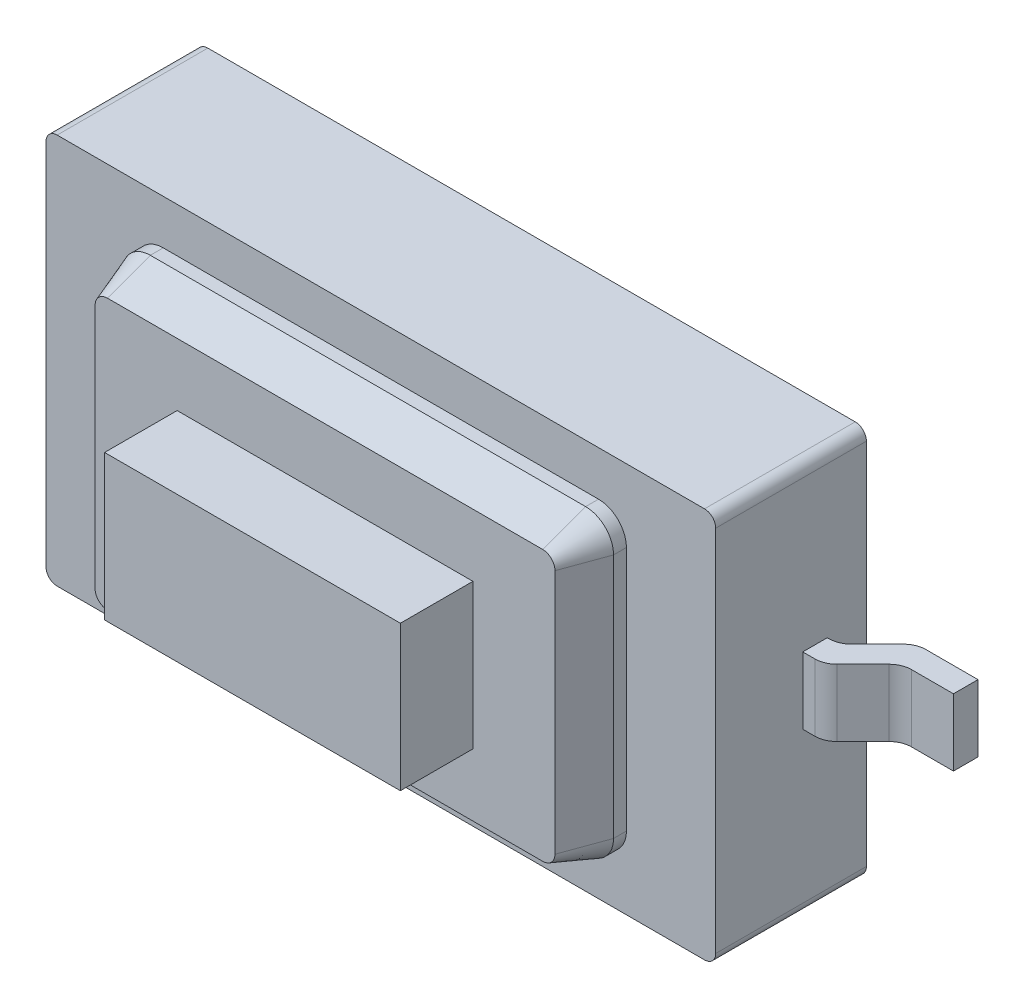
SolidWorks part; units mm, degrees
ref_plane "Front Plane" through (0, 0, 0) normal (0, 0, 1) x (1, 0, 0)
ref_plane "Top Plane" through (0, 0, 0) normal (0, 1, 0) x (1, 0, 0)
ref_plane "Right Plane" through (0, 0, 0) normal (1, 0, 0) x (0, 0, -1)
sketch "Sketch1" plane through (0, 0, 0) normal (0, 0, 1) x (1, 0, 0)
  line L0 (0, 6.8947) -> (0, -7.2797) construction
  line L2 (10.797, 0) -> (-8.2771, 0) construction
  line L3 (-2.9, 1.75) -> (2.9, 1.75)
  line L4 (-3, 1.65) -> (-3, -1.65)
  line L5 (-2.9, -1.75) -> (2.9, -1.75)
  line L6 (3, 1.65) -> (3, -1.65)
  line L7 (-1.325, 0.65) -> (1.325, 0.65)
  line L8 (-1.325, 0.65) -> (-1.325, -0.65)
  line L9 (-1.325, -0.65) -> (1.325, -0.65)
  line L10 (1.325, 0.65) -> (1.325, -0.65)
  line L11 (-1.95, 1.35) -> (1.95, 1.35)
  line L12 (-2.2, 1.1) -> (-2.2, -1.1)
  line L13 (-1.95, -1.35) -> (1.95, -1.35)
  line L14 (2.2, 1.1) -> (2.2, -1.1)
  arc A0 (-2.2, -1.1) -> (-1.95, -1.35) centre (-1.95, -1.1) ccw
  arc A1 (1.95, -1.35) -> (2.2, -1.1) centre (1.95, -1.1) ccw
  arc A2 (1.95, 1.35) -> (2.2, 1.1) centre (1.95, 1.1) cw
  arc A3 (-1.95, 1.35) -> (-2.2, 1.1) centre (-1.95, 1.1) ccw
  arc A4 (-3, -1.65) -> (-2.9, -1.75) centre (-2.9, -1.65) ccw
  arc A5 (2.9, -1.75) -> (3, -1.65) centre (2.9, -1.65) ccw
  arc A6 (2.9, 1.75) -> (3, 1.65) centre (2.9, 1.65) cw
  arc A7 (-2.9, 1.75) -> (-3, 1.65) centre (-2.9, 1.65) ccw
  dimension "D7" = 0.25
  dimension "D8" = 0.1
  dimension "D1" = 6
  dimension "D2" = 3.5
  dimension "D3" = 2.65
  dimension "D4" = 1.3
  dimension "D5" = 4.4
  dimension "D6" = 2.7
extrude "Boss-Extrude1" add sketch "Sketch1" along normal blind 1.35 contours L3 A6 L6 A5 L5 A4 L4 A7
extrude "Boss-Extrude2" add sketch "Sketch1<3>" along normal blind 1.85 contours L13 A1 L14 A2 L11 A3 L12 A0
sketch "Sketch1<3>" plane through (0, 0, 0) normal (0, 0, 1) x (1, 0, 0) same geometry as "Sketch1"
extrude "Boss-Extrude3" add sketch "Sketch1<4>" along normal blind 2.5 contours L9 L10 L7 L8
sketch "Sketch1<4>" plane through (0, 0, 0) normal (0, 0, 1) x (1, 0, 0) same geometry as "Sketch1"
chamfer "Chamfer1" distance 0.14 angle 70 7 edges at (0, -1.35, 1.85) (-2.1268, -1.2768, 1.85) (-2.2, 0, 1.85) (-2.1268, 1.2768, 1.85) (2.2, 0, 1.85) (2.1268, 1.2768, 1.85) (0, 1.35, 1.85) tangent propagation no first distance on face at (0, 0, 1.85)
sketch "Sketch2" plane through (0, 0, 0) normal (0, 1, 0) x (1, 0, 0)
  line L0 (3, -0.35) -> (3.0172, -0.35)
  line L1 (3.1586, -0.2914) -> (3.3914, -0.0586)
  line L2 (3.5328, 0) -> (4, 0)
  line L3 (4, 0) -> (4, -0.22)
  line L4 (4, -0.22) -> (3.624, -0.22)
  line L5 (3.4825, -0.2786) -> (3.2497, -0.5114)
  line L6 (3.1083, -0.57) -> (3, -0.57)
  line L7 (3, -0.57) -> (3, -0.35)
  line L8 (3, -1.35) -> (3, 0) construction
  line L9 (-2.9, 0) -> (2.9, 0) construction
  line L10 (0, -3.0718) -> (0, 0) construction
  arc A0 (3.2497, -0.5114) -> (3.1083, -0.57) centre (3.1083, -0.37) cw
  arc A1 (3.624, -0.22) -> (3.4825, -0.2786) centre (3.624, -0.42) ccw
  arc A2 (3.3914, -0.0586) -> (3.5328, 0) centre (3.5328, -0.2) cw
  arc A3 (3.0172, -0.35) -> (3.1586, -0.2914) centre (3.0172, -0.15) ccw
  point P15 (4, -0.11)
  point P24 (3.1, -0.35)
  dimension "D8" = 0.2
  dimension "D1" = 4
  dimension "D2" = 0.22
  dimension "D3" = 0.22
  dimension "D4" = 0.22
  dimension "D5" = 135
  dimension "D6" = 0.1
  dimension "D7" = 0.35
extrude "Boss-Extrude4" add sketch "Sketch2" along normal blind 0.3 and the other way blind 0.3
mirror "Mirror1" about plane through (0, 0, 0) normal (1, 0, 0) of "Boss-Extrude4"
